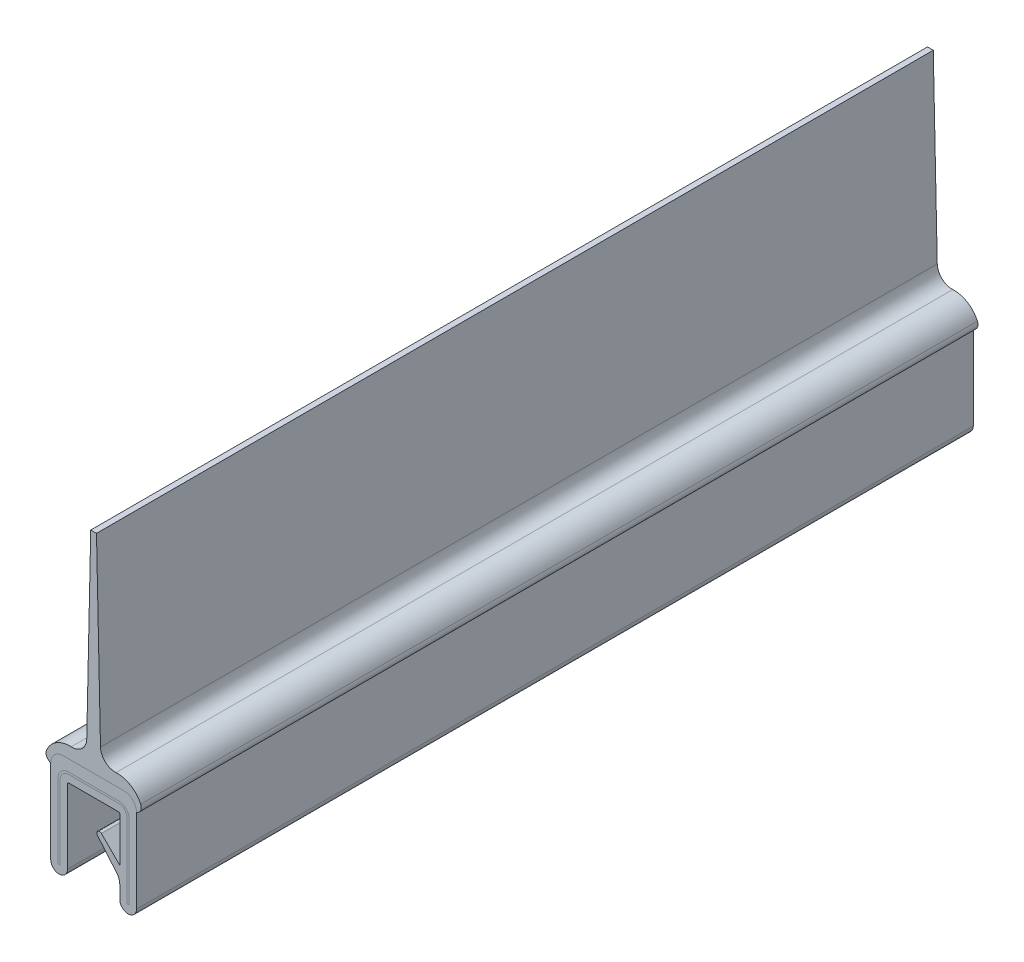
SolidWorks part; units mm, degrees
ref_plane "Front" through (0, 0, 0) normal (0, 0, 1) x (1, 0, 0)
ref_plane "Top" through (0, 0, 0) normal (0, 1, 0) x (1, 0, 0)
ref_plane "Right" through (0, 0, 0) normal (1, 0, 0) x (0, 0, -1)
sketch "Sketch1" plane through (0, 0, 0) normal (1, 0, 0) x (0, 0, -1)
  line L0 (152.4, 0) -> (-152.4, 0) construction
  point P2 (-127, 0)
  point P3 (127, 0)
  point P5 (0, 0)
  dimension "D1" = 25.4
  dimension "Length" = 304.8
  dimension "D2" = 25.4
sketch "Sketch2" plane through (0, 0, 0) normal (0, 0, 1) x (1, 0, 0)
  line L1 (-3.175, -12.7) -> (3.175, -12.7) construction
  line L2 (0, -12.7) -> (0, 0) construction
  line L3 (0, 0) -> (0, 25.4) construction
  point P4 (0, 0)
  point P8 (0, -12.7)
  dimension "Fits Edge Thickness" = 6.35
  dimension "Height" = 25.4
  dimension "Grip Height" = 12.7
sketch "Sketch4" plane through (0, 0, 0) normal (0, 0, 1) x (1, 0, 0)
  line L0 (-5.207, 0) -> (-5.207, -12.7) construction
  line L1 (-5.207, -12.7) -> (-3.175, -12.7)
  line L2 (-3.175, -12.7) -> (-3.175, -2.667)
  line L3 (-3.048, -2.54) -> (3.048, -2.54)
  line L4 (3.175, -2.667) -> (3.175, -8.0882)
  line L5 (3.175, -8.0882) -> (0.7184, -5.6316) construction
  line L6 (0, -6.35) -> (0.7184, -5.6316) construction
  line L7 (0, -6.35) -> (3.175, -9.525) construction
  line L8 (3.175, -9.525) -> (3.175, -12.7) construction
  line L9 (3.175, -12.7) -> (5.207, -12.7)
  line L10 (5.207, -12.7) -> (5.207, -1.524)
  line L11 (3.683, 0) -> (-3.683, 0)
  line L12 (0, -2.54) -> (0, 0) construction
  line L13 (-5.207, -1.524) -> (-5.207, -12.7)
  line L14 (3.175, -8.0882) -> (0.9484, -5.8615)
  line L16 (0, 0) -> (0, -12.7) construction
  line L17 (0.4693, -6.3005) -> (2.8036, -9.0824)
  line L24 (0, 0) -> (0, 25.4) construction
  line L25 (-1.5875, 0) -> (-1.5875, 0.6985) construction
  line L26 (1.5875, 0) -> (1.5875, 0.6985) construction
  line L27 (-1.5875, 0.6985) -> (-0.889, 0.6985) construction
  line L28 (1.5875, 0.6985) -> (0.889, 0.6985) construction
  line L29 (-0.889, 0.6985) -> (-0.3492, 25.4) construction
  line L30 (0.889, 0.6985) -> (0.3492, 25.4) construction
  line L31 (-0.3492, 25.4) -> (0.3492, 25.4) construction
  line L32 (3.175, -10.1028) -> (3.175, -12.7)
  line L33 (5.207, -1.524) -> (5.207, 0) construction
  line L34 (5.207, 0) -> (3.683, 0) construction
  arc A2 (0.9484, -5.8615) -> (0.4693, -6.3005) centre (0.7184, -6.0915) ccw
  arc A3 (5.207, -1.524) -> (3.683, 0) centre (3.683, -1.524) ccw
  arc A4 (-5.207, -1.524) -> (-3.683, 0) centre (-3.683, -1.524) cw
  arc A5 (3.048, -2.54) -> (3.175, -2.667) centre (3.048, -2.667) cw
  arc A6 (-3.175, -2.667) -> (-3.048, -2.54) centre (-3.048, -2.667) cw
  arc A7 (2.8036, -9.0824) -> (3.175, -10.1028) centre (1.5875, -10.1028) cw
  point P0 (0, -2.54)
  point P19 (1.6365, -7.6914)
  point P22 (0, 0)
  dimension "D5" = 1.524
  dimension "D2" = 0.127
  dimension "D11" = 1.5875
  dimension "D4" = 1.016
  dimension "D3" = 2.54
  dimension "D7" = 3.175
  dimension "D8" = 3.175
  dimension "D9" = 1.778
  dimension "D1" = 2.032
  dimension "D6" = 135
  dimension "D10" = 5
extrude "Boss-Extrude1" add sketch "Sketch4" along normal up to vertex (152.4 mm away) and the other way up to vertex (152.4 mm away) up to point (0, 0, 152.4) other way up to point (0, 0, -152.4)
sketch "Sketch3" plane through (0, 0, 0) normal (0, 0, 1) x (1, 0, 0)
  line L0 (-0.889, 0.6985) -> (-0.3492, 25.4) construction
  line L1 (3.683, 0) -> (-3.683, 0) construction
  line L2 (-0.3492, 25.4) -> (0.3492, 25.4) construction
  line L3 (0.889, 0.6985) -> (0.3492, 25.4) construction
  line L4 (3.683, 0) -> (-3.683, 0)
  line L5 (3.683, 0.762) -> (-3.683, 0.762) construction
  line L6 (1.5875, 0.6985) -> (0.889, 0.6985) construction
  line L7 (-3.683, 0.762) -> (-1.5875, 0.6985) construction
  line L8 (-1.5875, 0.6985) -> (-0.889, 0.6985) construction
  line L9 (-5.207, -1.524) -> (-5.9305, -1.1063)
  line L10 (5.207, -1.524) -> (5.9305, -1.1063)
  line L11 (1.5875, 0.6985) -> (3.683, 0.762) construction
  line L13 (0, 0) -> (0, 25.4) construction
  line L14 (-0.8349, 3.175) -> (-0.3492, 25.4)
  line L15 (-0.889, 0.6985) -> (-0.3492, 25.4) construction
  line L16 (-0.3492, 25.4) -> (0.3492, 25.4)
  line L17 (0.889, 0.6985) -> (0.3492, 25.4) construction
  line L18 (1.5875, 0.6985) -> (0.889, 0.6985) construction
  line L19 (0.3492, 25.4) -> (0.8349, 3.175)
  line L20 (-1.5875, 0.6985) -> (-0.889, 0.6985) construction
  arc A0 (-3.683, 0) -> (-5.207, -1.524) centre (-3.683, -1.524) ccw construction
  arc A1 (5.207, -1.524) -> (3.683, 0) centre (3.683, -1.524) ccw construction
  arc A2 (-3.683, 0) -> (-5.207, -1.524) centre (-3.683, -1.524) ccw
  arc A3 (5.207, -1.524) -> (3.683, 0) centre (3.683, -1.524) ccw
  arc A4 (5.9305, -1.1063) -> (3.683, 0.762) centre (3.683, -1.524) ccw construction
  arc A5 (-3.683, 0.762) -> (-5.9305, -1.1063) centre (-3.683, -1.524) ccw construction
  arc A6 (-3.683, 0.762) -> (-5.969, -1.524) centre (-3.683, -1.524) ccw construction
  arc A7 (5.969, -1.524) -> (3.683, 0.762) centre (3.683, -1.524) ccw construction
  arc A8 (2.7213, 1.4231) -> (5.9305, -1.1063) centre (2.8826, -1.6728) cw
  arc A9 (2.7213, 1.4231) -> (0.8349, 3.175) centre (2.6279, 3.2142) cw
  arc A10 (-2.7213, 1.4231) -> (-5.9305, -1.1063) centre (-2.8826, -1.6728) ccw
  arc A11 (-2.7213, 1.4231) -> (-0.8349, 3.175) centre (-2.6279, 3.2142) ccw
  point P29 (4.8016, 0.762)
  dimension "D1" = 0.762
  dimension "D3" = 30
  dimension "D4" = 3.175
extrude "Boss-Extrude2" add sketch "Sketch3" along normal up to vertex (152.4 mm away) and the other way up to vertex (152.4 mm away) separate body up to point (0, 0, 152.4) other way up to point (0, 0, -152.4)
fillet "Fillet1" radius 0.7937 2 edges at (5.9305, -1.1063, 0) (-5.9305, -1.1063, 0)
sketch "Sketch5" plane through (0, 0, 0) normal (0, 0, 1) x (1, 0, 0)
  line L0 (4.191, -11.684) -> (4.191, -2.667) construction
  line L2 (3.048, -1.524) -> (-3.048, -1.524) construction
  line L3 (-4.191, -2.667) -> (-4.191, -11.684) construction
  line L4 (4.191, -12.7) -> (4.191, -11.684) construction
  line L7 (3.175, -12.7) -> (5.207, -12.7) construction
  line L8 (4.318, -11.684) -> (4.318, -2.667)
  line L9 (3.048, -1.397) -> (-3.048, -1.397)
  line L10 (-4.318, -2.667) -> (-4.318, -11.684)
  line L11 (4.064, -11.684) -> (4.064, -2.667)
  line L12 (3.048, -1.651) -> (-3.048, -1.651)
  line L13 (-4.064, -2.667) -> (-4.064, -11.684)
  line L14 (4.318, -11.684) -> (4.064, -11.684)
  line L15 (-4.318, -11.684) -> (-4.064, -11.684)
  arc A0 (4.191, -2.667) -> (3.048, -1.524) centre (3.048, -2.667) ccw construction
  arc A1 (-3.048, -1.524) -> (-4.191, -2.667) centre (-3.048, -2.667) ccw construction
  arc A3 (3.175, -2.667) -> (3.048, -2.54) centre (3.048, -2.667) ccw construction
  arc A4 (-3.048, -2.54) -> (-3.175, -2.667) centre (-3.048, -2.667) ccw construction
  arc A5 (4.318, -2.667) -> (3.048, -1.397) centre (3.048, -2.667) ccw
  arc A6 (-3.048, -1.397) -> (-4.318, -2.667) centre (-3.048, -2.667) ccw
  arc A7 (4.064, -2.667) -> (3.048, -1.651) centre (3.048, -2.667) ccw
  arc A8 (-3.048, -1.651) -> (-4.064, -2.667) centre (-3.048, -2.667) ccw
  dimension "D2" = 0.127
  dimension "D1" = 1.016
  dimension "D3" = 0.127
extrude "Cut-Extrude1" cut sketch "Sketch5" against normal through all both and the other way through all
extrude "Boss-Extrude3" add sketch "Sketch5<2>" along normal through all and the other way through all separate body
sketch "Sketch5<2>" plane through (0, 0, 0) normal (0, 0, 1) x (1, 0, 0) same geometry as "Sketch5"
fillet "Fillet2" 2 edges at (5.207, -12.7, 0) (3.175, -12.7, 0) type full round first side face at (5.207, -7.112, 0) second side face at (3.175, -11.4014, 0) middle face at (4.191, -12.7, 0)
fillet "Fillet3" 2 edges at (-5.207, -12.7, 0) (-3.175, -12.7, 0) type full round first side face at (-5.207, -7.112, 0) second side face at (-3.175, -7.6835, 0) middle face at (-4.191, -12.7, 0)
sketch "Sketch6" plane through (0, 0, 0) normal (1, 0, 0) x (0, 0, -1)
  line L0 (-152.4, -12.7) -> (152.4, -12.7) construction
  line L1 (152.4, 25.4) -> (-50.8, 25.4)
  line L2 (152.4, 25.4) -> (152.4, -12.7)
  line L3 (152.4, -12.7) -> (-50.8, -12.7)
  line L4 (-50.8, 25.4) -> (-50.8, -12.7)
  line L5 (-152.4, 3.175) -> (-152.4, 25.4) construction
  dimension "D1" = 101.6
extrude "Cut-Extrude2" cut sketch "Sketch6" against normal through all and the other way through all
equation "\"D4@Sketch4\" = \"D1@Sketch4\" / 2"
equation "\"D7@Sketch4\"=\"Grip Height@Sketch2\" / 4"
equation "\"D1@Sketch5\"=\"D1@Sketch4\"/2"
equation "\"D11@Sketch4\"=\"D7@Sketch4\"/2"
